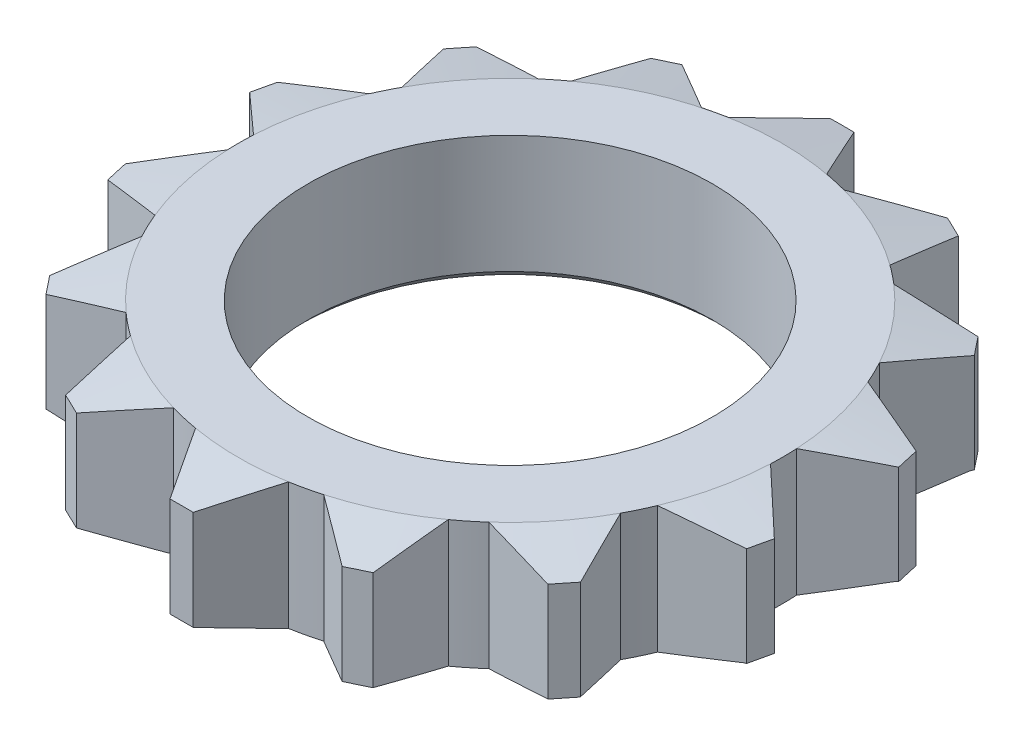
SolidWorks part; units mm, degrees
ref_plane "Front Plane" through (0, 0, 0) normal (0, 0, 1) x (1, 0, 0)
ref_plane "Top Plane" through (0, 0, 0) normal (0, 1, 0) x (1, 0, 0)
ref_plane "Right Plane" through (0, 0, 0) normal (1, 0, 0) x (0, 0, -1)
sketch "Sketch1" plane through (0, 0, 0) normal (0, 1, 0) x (1, 0, 0)
  line L0 (0, 0) -> (0, 18.32) construction
  line L1 (2.69, 14.7707) -> (0.6408, 18.32)
  line L2 (0.6408, 18.32) -> (-0.6408, 18.32)
  line L3 (-0.6408, 18.32) -> (-2.69, 14.7707)
  line L4 (-2.69, 14.7707) -> (-3.94, 14.4875)
  line L5 (3.9391, 14.4836) -> (2.69, 14.7707)
  line L6 (7.3253, 16.7923) -> (3.9391, 14.4836)
  line L7 (8.4801, 16.2362) -> (7.3253, 16.7923)
  line L8 (8.7863, 12.1493) -> (8.4801, 16.2362)
  line L9 (9.7871, 11.3486) -> (8.7863, 12.1493)
  line L10 (13.8397, 11.9594) -> (9.7871, 11.3486)
  line L11 (14.6388, 10.9574) -> (13.8397, 11.9594)
  line L12 (13.1415, 7.1423) -> (14.6388, 10.9574)
  line L13 (13.6958, 5.9867) -> (13.1415, 7.1423)
  line L14 (17.6121, 4.7787) -> (13.6958, 5.9867)
  line L15 (17.8973, 3.5292) -> (17.6121, 4.7787)
  line L16 (14.893, 0.7416) -> (17.8973, 3.5292)
  line L17 (14.891, -0.5401) -> (14.893, 0.7416)
  line L18 (17.8953, -3.3277) -> (14.891, -0.5401)
  line L19 (17.6101, -4.5772) -> (17.8953, -3.3277)
  line L20 (13.6938, -5.7852) -> (17.6101, -4.5772)
  line L21 (13.1359, -6.9391) -> (13.6938, -5.7852)
  line L22 (14.6332, -10.7541) -> (13.1359, -6.9391)
  line L23 (13.8341, -11.7562) -> (14.6332, -10.7541)
  line L24 (9.7815, -11.1453) -> (13.8341, -11.7562)
  line L25 (8.7782, -11.9429) -> (9.7815, -11.1453)
  line L26 (8.472, -16.0298) -> (8.7782, -11.9429)
  line L27 (7.3172, -16.5859) -> (8.472, -16.0298)
  line L28 (3.931, -14.2772) -> (7.3172, -16.5859)
  line L29 (2.681, -14.5604) -> (3.931, -14.2772)
  line L30 (0.6319, -18.1097) -> (2.681, -14.5604)
  line L31 (-0.6498, -18.1097) -> (0.6319, -18.1097)
  line L32 (-2.699, -14.5604) -> (-0.6498, -18.1097)
  line L33 (-3.9481, -14.2733) -> (-2.699, -14.5604)
  line L34 (-7.3343, -16.582) -> (-3.9481, -14.2733)
  line L35 (-8.489, -16.0259) -> (-7.3343, -16.582)
  line L36 (-8.7953, -11.939) -> (-8.489, -16.0259)
  line L37 (-9.7961, -11.1383) -> (-8.7953, -11.939)
  line L38 (-13.8487, -11.7491) -> (-9.7961, -11.1383)
  line L39 (-14.6478, -10.7471) -> (-13.8487, -11.7491)
  line L40 (-13.1505, -6.9321) -> (-14.6478, -10.7471)
  line L41 (-13.7048, -5.7764) -> (-13.1505, -6.9321)
  line L42 (-17.6211, -4.5684) -> (-13.7048, -5.7764)
  line L43 (-17.9063, -3.3189) -> (-17.6211, -4.5684)
  line L44 (-14.902, -0.5313) -> (-17.9063, -3.3189)
  line L45 (-14.9, 0.7504) -> (-14.902, -0.5313)
  line L46 (-17.9043, 3.5379) -> (-14.9, 0.7504)
  line L47 (-17.6191, 4.7875) -> (-17.9043, 3.5379)
  line L48 (-13.7028, 5.9955) -> (-17.6191, 4.7875)
  line L49 (-13.1449, 7.1494) -> (-13.7028, 5.9955)
  line L50 (-14.6422, 10.9644) -> (-13.1449, 7.1494)
  line L51 (-13.8431, 11.9665) -> (-14.6422, 10.9644)
  line L52 (-9.7905, 11.3556) -> (-13.8431, 11.9665)
  line L53 (-8.7872, 12.1532) -> (-9.7905, 11.3556)
  line L54 (-8.4809, 16.2401) -> (-8.7872, 12.1532)
  line L55 (-7.3262, 16.7962) -> (-8.4809, 16.2401)
  line L56 (-3.94, 14.4875) -> (-7.3262, 16.7962)
  circle A0 centre (0, 0) radius 15
  circle A1 centre (0, 0) radius 18.32
  point P10 (0, 18.32)
  point P14 (-3.315, 14.6291)
  dimension "D1" = 30
  dimension "D2" = 3.32
  dimension "D3" = 120
  dimension "D4" = 120
  dimension "D5" = 6.63
  dimension "D6" = 14
extrude "Boss-Extrude1" add sketch "Sketch1" along normal blind 7 contours L28 A0 L26 L25 L24 L22 L21 L20 L18 L17 L16 L14 L13 L12 L10 L9 L8 L5 L54 L53 L52 L50 L49 L48 L46 L45 L44 L42 L41 L40 L38 L37 L36 L34 L33 L32 | A0 L48 L47 L46 | A0 L44 L43 L42 | A0 L40 L39 L38 | A0 L36 L35 L34 | A0 L28 L27 L26 | A0 L32 L31 L30 | A0 L24 L23 L22 | A0 L20 L19 L18 | A0 L16 L15 L14 | A0 L12 L11 L10 | L7 A1 L6 L5 A0 L8 | L0 A0 L5 L1 A1 | A0 L0 A1 L3 L4 | L56 A1 L55 L54 A0 L4 | A0 L52 L51 L50 | A0 region at (-0.936, 0, -16.2753) region at (0.9359, 0, -16.2754) region at (-0.0009, 0, -0.0221) region at (-7.0154, 0, -14.6839) region at (7.0161, 0, -14.6824) region at (-12.6598, 0, -10.2117) region at (12.6602, 0, -10.2074) region at (-15.8178, 0, -3.7276) region at (15.8167, 0, -3.7196) region at (-15.8538, 0, 3.4991) region at (15.8484, 0, 3.5101) region at (-12.7418, 0, 10.038) region at (12.7302, 0, 10.0488) region at (-7.0859, 0, 14.5797) region at (7.0688, 0, 14.5865) region at (-0.0097, 0, 16.2062)
sketch "Sketch2" plane through (0, 0, 0) normal (0, -1, 0) x (1, 0, 0)
  circle A0 centre (0, 0) radius 11.15
  dimension "D1" = 22.3
extrude "Cut-Extrude1" cut sketch "Sketch2" against normal through all both and the other way through all
sketch "Sketch3" plane through (0, 0, 0) normal (1, 0, 0) x (0, 0, -1)
  line L0 (11.15, 7) -> (-11.15, 7) construction
  line L1 (11.15, 7) -> (-11.15, 7)
  line L2 (-11.15, 0) -> (11.15, 0) construction
  line L3 (-11.15, 0) -> (11.15, 0)
  line L4 (-18.1097, 0) -> (-14.781, 0) construction
  line L5 (-15, 7) -> (15, 7) construction
  line L6 (-15, 7) -> (-15, 0)
  line L7 (-15, 0) -> (15, 0) construction
  line L8 (15, 7) -> (15, 0)
  line L9 (-18.1097, 7) -> (-14.781, 7) construction
  line L10 (-18.1097, 0) -> (-14.781, 0)
  line L11 (-18.1097, 7) -> (-14.781, 7)
  line L12 (-18.1097, 6.25) -> (-18.6097, 6.1294)
  line L14 (-18.1097, 7) -> (-18.1097, 0)
  line L15 (-18.1097, 6.25) -> (-15, 7)
  line L16 (-18.1097, 0.75) -> (-15, 0)
  line L17 (0, 7) -> (0, 0) construction
  line L19 (-15, 7.5) -> (-18.6097, 7.5)
  line L20 (-15, 7.5) -> (-15, 6.25)
  line L21 (-15, 6.25) -> (-18.1097, 6.25)
  line L22 (-18.6097, 7.5) -> (-18.6097, 6.1294)
  line L23 (-15, -0.5) -> (-18.6097, -0.5)
  line L24 (-15, -0.5) -> (-15, 0.75)
  line L25 (-15, 0.75) -> (-18.6097, 0.75)
  line L26 (-18.6097, -0.5) -> (-18.6097, 0.75)
  point P8 (0, 0)
  point P10 (-18.6097, 6.25)
  point P27 (-18.6097, 6.2932)
  point P28 (-18.6097, 6.2086)
  point P30 (-18.6097, 6.1364)
  dimension "D1" = 30
  dimension "D2" = 0.75
  dimension "D3" = 0.75
  dimension "D4" = 0.5
  dimension "D5" = 0.5
  dimension "D6" = 0.5
revolve "Cut-Revolve2" cut sketch "Sketch3" angle 360 about L17 region at (0, 6.75, 17.0731) region at (0, 7.1298, 17.091) region at (0, 0.25, 17.0731) region at (0, -0.1425, 17.0723)
chamfer "Chamfer1" distance 0.5 angle 45 1 edges at (0, 0, 11.15)
equation "\"D6@Sketch1\"=\"D1@Sketch1\"*3.1415/\"D5@Sketch1\""
